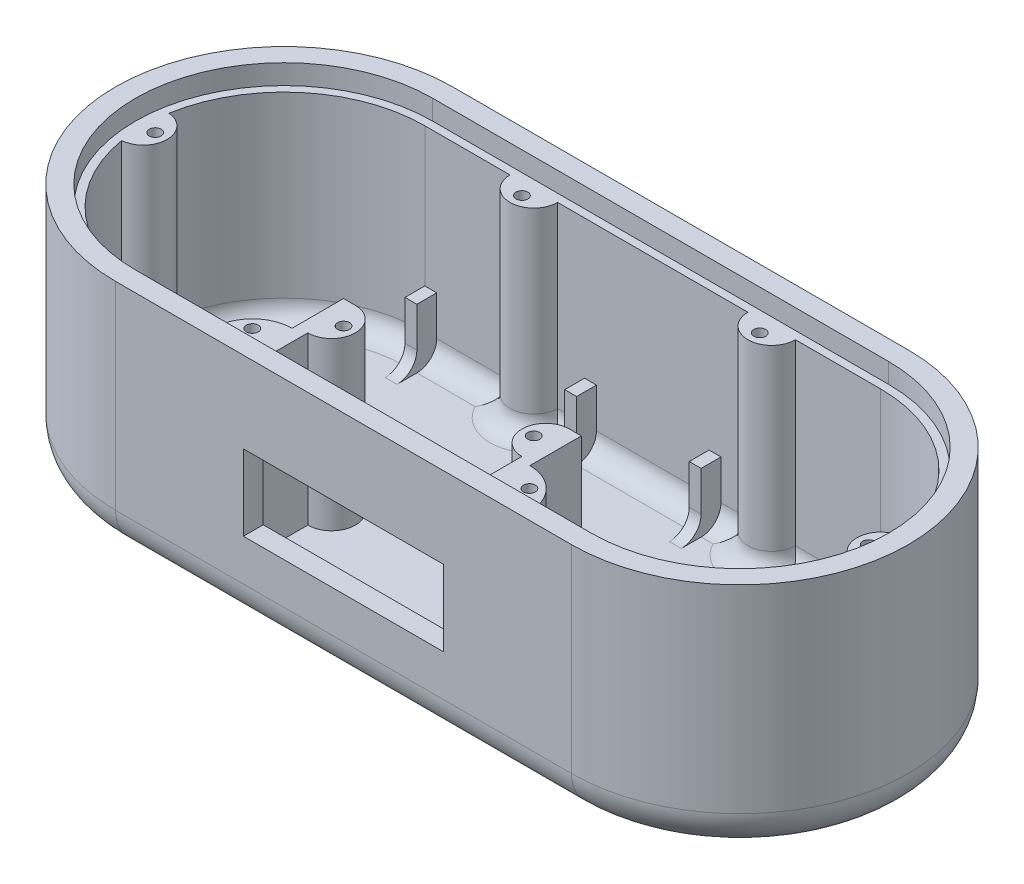
SolidWorks part; units mm, degrees
ref_plane "Front Plane" through (0, 0, 0) normal (0, 0, 1) x (1, 0, 0)
ref_plane "Top Plane" through (0, 0, 0) normal (0, 1, 0) x (1, 0, 0)
ref_plane "Right Plane" through (0, 0, 0) normal (1, 0, 0) x (0, 0, -1)
sketch "Sketch1" plane through (0, 0, 0) normal (0, 1, 0) x (1, 0, 0)
  line L0 (-57.5, 0) -> (57.5, 0) construction
  line L1 (-57.5, 42.5) -> (57.5, 42.5)
  line L2 (-57.5, -42.5) -> (57.5, -42.5)
  line L3 (-57.5, 0) -> (-100, 0) construction
  line L4 (57.5, 0) -> (100, 0) construction
  arc A0 (-57.5, 42.5) -> (-57.5, -42.5) centre (-57.5, 0) ccw
  arc A1 (57.5, -42.5) -> (57.5, 42.5) centre (57.5, 0) ccw
  point P3 (0, 0)
  point P12 (31.5337, 0)
  point P13 (0, 0)
  dimension "D1" = 85
  dimension "D2" = 200
extrude "Boss-Extrude1" add sketch "Sketch1" along normal blind 60
fillet "Fillet1" radius 10 4 edges at (0, 0, 42.5) (100, 0, 0) (0, 0, -42.5) (-100, 0, 0)
sketch "Sketch2" plane through (0, 60, 0) normal (0, 1, 0) x (1, 0, 0)
  line L2 (-57.5, -37.5) -> (-30, -37.5)
  line L3 (-30, -37.5) -> (-30, -12.5)
  line L4 (-57.5, -37.5) -> (57.5, -37.5)
  line L5 (57.5, 37.5) -> (-57.5, 37.5)
  line L7 (57.5, 37.5) -> (-57.5, 37.5)
  line L8 (-30, -12.5) -> (30, -12.5)
  line L9 (30, -12.5) -> (30, -37.5)
  line L10 (30, -37.5) -> (57.5, -37.5)
  line L11 (0, -12.5) -> (0, 0) construction
  arc A4 (-57.5, 37.5) -> (-57.5, -37.5) centre (-57.5, 0) ccw
  arc A5 (57.5, -37.5) -> (57.5, 37.5) centre (57.5, 0) ccw
  arc A6 (-57.5, 37.5) -> (-57.5, -37.5) centre (-57.5, 0) ccw
  arc A7 (57.5, -37.5) -> (57.5, 37.5) centre (57.5, 0) ccw
  dimension "D2" = 25
  dimension "D3" = 60
  dimension "D1" = 5
extrude "Cut-Extrude1" cut sketch "Sketch2" against normal blind 5
sketch "Sketch3" plane through (0, 55, 0) normal (0, 1, 0) x (1, 0, 0)
  line L0 (30, -12.5) -> (30, -37.5) construction
  line L1 (-30, -37.5) -> (-30, -12.5) construction
  line L2 (-30, -25.5) -> (30, -25.5) construction
  line L3 (-40, -35.5) -> (-30, -35.5) construction
  line L4 (40, -35.5) -> (30, -35.5) construction
  line L5 (-37.0711, -28.4289) -> (-30, -35.5) construction
  line L6 (-30, -37.5) -> (-30, -12.5) construction
  line L7 (30, -35.5) -> (37.0711, -28.4289) construction
  line L8 (-30, 32.5) -> (-30, 35.5) construction
  line L9 (30, 35.5) -> (30, 32.5) construction
  line L10 (-36, 35.5) -> (-57.5, 35.5)
  line L11 (24, 35.5) -> (-24, 35.5)
  line L12 (32, -35.5) -> (57.5, -35.5)
  line L13 (57.5, 35.5) -> (-57.5, 35.5)
  line L14 (-57.5, -35.5) -> (-32, -35.5)
  line L15 (-32, -35.5) -> (-32, -10.5)
  line L16 (-32, -10.5) -> (32, -10.5)
  line L17 (32, -10.5) -> (32, -35.5)
  line L18 (40, -35.5) -> (57.5, -35.5)
  line L19 (57.5, 35.5) -> (36, 35.5)
  line L20 (-57.5, -35.5) -> (-40, -35.5)
  line L21 (93, 0) -> (95, 0) construction
  line L24 (-93, 0) -> (-95, 0) construction
  line L25 (-34.9497, -30.5503) -> (34.9497, -30.5503) construction
  line L26 (-90, 0) -> (-87, 0) construction
  line L27 (90, 0) -> (87, 0) construction
  line L28 (30, 32.5) -> (30, 29.5) construction
  line L29 (-30, 32.5) -> (-30, 29.5) construction
  line L30 (-30, 29.5) -> (-30, -12.5) construction
  line L31 (30, 29.5) -> (30, -12.5) construction
  line L32 (-30, -25.5) -> (-30, -12.5)
  line L33 (-30, -12.5) -> (30, -12.5)
  line L34 (30, -12.5) -> (30, -25.5)
  arc A0 (40, -35.5) -> (30, -25.5) centre (30, -35.5) ccw
  arc A1 (-92.493, 5.9785) -> (-92.493, -5.9785) centre (-93, 0) cw
  arc A2 (-30, -25.5) -> (-40, -35.5) centre (-30, -35.5) ccw
  arc A3 (92.493, 5.9785) -> (92.493, -5.9785) centre (93, 0) ccw
  arc A4 (57.5, -35.5) -> (57.5, 35.5) centre (57.5, 0) ccw
  arc A5 (-57.5, 35.5) -> (-57.5, -35.5) centre (-57.5, 0) ccw
  arc A6 (57.5, -35.5) -> (92.493, -5.9785) centre (57.5, 0) ccw
  arc A7 (-57.5, 35.5) -> (-92.493, 5.9785) centre (-57.5, 0) ccw
  arc A8 (24, 35.5) -> (36, 35.5) centre (30, 35.5) ccw
  arc A9 (-36, 35.5) -> (-24, 35.5) centre (-30, 35.5) ccw
  arc A10 (-92.493, -5.9785) -> (-57.5, -35.5) centre (-57.5, 0) ccw
  arc A11 (92.493, 5.9785) -> (57.5, 35.5) centre (57.5, 0) ccw
  arc A12 (57.5, -37.5) -> (57.5, 37.5) centre (57.5, 0) ccw construction
  arc A13 (-57.5, 37.5) -> (-57.5, -37.5) centre (-57.5, 0) ccw construction
  arc A14 (-92.493, 5.9785) -> (-93, 0) centre (-57.5, 0) ccw construction
  arc A15 (-92.493, -5.9785) -> (-93, 0) centre (-57.5, 0) cw construction
  arc A16 (92.493, 5.9785) -> (93, 0) centre (57.5, 0) cw construction
  arc A17 (92.493, -5.9785) -> (93, 0) centre (57.5, 0) ccw construction
  circle A18 centre (-90, 0) radius 1.5
  circle A19 centre (-30, 32.5) radius 1.5
  circle A20 centre (30, 32.5) radius 1.5
  circle A21 centre (90, 0) radius 1.5
  circle A22 centre (34.9497, -30.5503) radius 1.5
  circle A23 centre (-34.9497, -30.5503) radius 1.5
  dimension "D2" = 10
  dimension "D3" = 6
  dimension "D4" = 3
  dimension "D5" = 3
  dimension "D6" = 42
  dimension "D7" = 3
  dimension "D1" = 2
extrude "Cut-Extrude2" cut sketch "Sketch3" against normal offset from surface (50 mm away) 5 up to face at (0, 0, 0)
fillet "Fillet2" radius 5 18 edges at (-48.75, 5, 35.5) (-80.3912, 5, 27.1338) (-87, 5, 0) (-80.3912, 5, -27.1338) (-46.75, 5, -35.5) (-30, 5, -29.5) (0, 5, -35.5) (30, 5, -29.5) (46.75, 5, -35.5) (80.3912, 5, -27.1338) (87, 5, 0) (80.3912, 5, 27.1338) (48.75, 5, 35.5) (37.0711, 5, 28.4289) (30, 5, 19) (0, 5, 12.5) (-30, 5, 19) (-37.0711, 5, 28.4289)
sketch "Sketch4" plane through (0, 55, 0) normal (0, 1, 0) x (1, 0, 0)
  line L5 (-57.5, -30.5) -> (-44.1421, -30.5) construction
  line L10 (-57.5, -35.5) -> (-54.5, -35.5)
  line L11 (-57.5, -35.5) -> (-57.5, -30.5)
  line L12 (-57.5, -30.5) -> (-54.5, -30.5)
  line L13 (-54.5, -35.5) -> (-54.5, -30.5)
  line L14 (24, 35.5) -> (-24, 35.5) construction
  line L15 (-17.202, 35.5) -> (-14.202, 35.5)
  line L16 (-17.202, 35.5) -> (-17.202, 30.5)
  line L17 (-17.202, 30.5) -> (-14.202, 30.5)
  line L18 (-14.202, 35.5) -> (-14.202, 30.5)
  line L19 (20.202, 30.5) -> (-20.202, 30.5) construction
  line L20 (-39.798, 30.5) -> (-57.5, 30.5) construction
  line L21 (17.202, 35.5) -> (14.202, 35.5)
  line L22 (17.202, 35.5) -> (17.202, 30.5)
  line L23 (17.202, 30.5) -> (14.202, 30.5)
  line L24 (14.202, 35.5) -> (14.202, 30.5)
  line L25 (-57.5, 35.5) -> (-54.5, 35.5)
  line L26 (-57.5, 35.5) -> (-57.5, 30.5)
  line L27 (-57.5, 30.5) -> (-54.5, 30.5)
  line L28 (-54.5, 35.5) -> (-54.5, 30.5)
  line L29 (57.5, 30.5) -> (39.798, 30.5) construction
  line L30 (57.5, 35.5) -> (54.5, 35.5)
  line L31 (57.5, 35.5) -> (57.5, 30.5)
  line L32 (57.5, 30.5) -> (54.5, 30.5)
  line L33 (54.5, 35.5) -> (54.5, 30.5)
  line L34 (44.1421, -30.5) -> (57.5, -30.5) construction
  line L35 (57.5, -35.5) -> (54.5, -35.5)
  line L36 (57.5, -35.5) -> (57.5, -30.5)
  line L37 (57.5, -30.5) -> (54.5, -30.5)
  line L38 (54.5, -35.5) -> (54.5, -30.5)
  dimension "D1" = 3
  dimension "D2" = 3
  dimension "D3" = 3
extrude "Boss-Extrude2" add sketch "Sketch4" against normal up to surface (50 mm away) up to face at (0, 5, 0.3691)
sketch "Sketch5" plane through (0, 55, 0) normal (0, 1, 0) x (1, 0, 0)
  line L1 (-57.5, 30.5) -> (-54.5, 30.5)
  line L2 (-57.5, 30.5) -> (-57.5, 35.5)
  line L3 (-57.5, 35.5) -> (-54.5, 35.5)
  line L4 (-54.5, 30.5) -> (-54.5, 35.5)
  line L5 (-17.202, 30.5) -> (-14.202, 30.5)
  line L6 (-17.202, 30.5) -> (-17.202, 35.5)
  line L7 (-17.202, 35.5) -> (-14.202, 35.5)
  line L8 (-14.202, 30.5) -> (-14.202, 35.5)
  line L9 (14.202, 30.5) -> (17.202, 30.5)
  line L10 (14.202, 30.5) -> (14.202, 35.5)
  line L11 (14.202, 35.5) -> (17.202, 35.5)
  line L12 (17.202, 30.5) -> (17.202, 35.5)
  line L13 (54.5, 30.5) -> (57.5, 30.5)
  line L14 (54.5, 30.5) -> (54.5, 35.5)
  line L15 (54.5, 35.5) -> (57.5, 35.5)
  line L16 (57.5, 30.5) -> (57.5, 35.5)
  line L17 (54.5, -30.5) -> (57.5, -30.5)
  line L18 (54.5, -30.5) -> (54.5, -35.5)
  line L19 (54.5, -35.5) -> (57.5, -35.5)
  line L20 (57.5, -30.5) -> (57.5, -35.5)
  line L21 (-57.5, -30.5) -> (-54.5, -30.5)
  line L22 (-57.5, -30.5) -> (-57.5, -35.5)
  line L23 (-57.5, -35.5) -> (-54.5, -35.5)
  line L24 (-54.5, -30.5) -> (-54.5, -35.5)
extrude "Cut-Extrude3" cut sketch "Sketch5" against normal offset from surface (35 mm away) 15 up to face at (0, 5, -4.4367)
fillet "Fillet3" radius 5 6 edges at (15.702, 5, -30.5) (-56, 5, 30.5) (56, 5, 30.5) (56, 5, -30.5) (-15.702, 5, -30.5) (-56, 5, -30.5)
sketch "Sketch6" plane through (0, 5, 0) normal (0, 1, 0) x (1, 0, 0)
  circle A0 centre (-57.5, 0) radius 3
  circle A1 centre (-57.5, 0) radius 1.5
  circle A2 centre (57.5, 0) radius 3
  circle A3 centre (57.5, 0) radius 1.5
  arc A4 (-57.5, 30.5) -> (-86.6479, 8.9806) centre (-57.5, 0) ccw construction
  arc A5 (86.6479, 8.9806) -> (57.5, 30.5) centre (57.5, 0) ccw construction
  dimension "D1" = 3
  dimension "D2" = 6
extrude "Boss-Extrude3" add sketch "Sketch6" along normal up to surface (15 mm away) up to face at (-56, 20, -33)
fillet "Fillet4" radius 1 2 edges at (57.5, 5, 3) (-57.5, 5, 3)
sketch "Sketch8" plane through (0, 0, 12.5) normal (0, 0, -1) x (-1, 0, 0)
  line L5 (-57.5, 60) -> (57.5, 60) construction
  line L6 (-30, 60) -> (30, 60)
  line L8 (-27, 57) -> (-27, 13)
  line L9 (-27, 13) -> (27, 13)
  line L10 (27, 13) -> (27, 57)
  line L11 (27, 57) -> (-27, 57)
  line L12 (-27, 57) -> (-27, 13)
  line L13 (-27, 13) -> (27, 13)
  line L14 (27, 13) -> (27, 57)
  line L16 (30, 60) -> (-30, 60) construction
  line L17 (27, 57) -> (30, 57)
  line L18 (30, 10) -> (30, 60) construction
  line L19 (30, 57) -> (30, 60)
  line L20 (-27, 57) -> (-30, 57)
  line L21 (-30, 10) -> (-30, 60) construction
  line L22 (-30, 57) -> (-30, 60)
  dimension "D1" = 3
extrude "Cut-Extrude4" cut sketch "Sketch8" against normal offset from surface (25 mm away) 5 up to face at (0, 35, 42.5)
sketch "Sketch10" plane through (0, 0, 37.5) normal (0, 0, -1) x (-1, 0, 0)
  line L5 (0, 39.55) -> (0, 60) construction
  line L7 (-25.25, 39.55) -> (25.25, 39.55)
  line L9 (-25.25, 39.55) -> (-25.25, 20.45)
  line L10 (-25.25, 20.45) -> (25.25, 20.45)
  line L11 (25.25, 39.55) -> (25.25, 20.45)
  line L12 (-57.5, 60) -> (57.5, 60) construction
  line L13 (0, 20.45) -> (0, 0) construction
  dimension "D1" = 19.1
  dimension "D2" = 50.5
extrude "Cut-Extrude5" cut sketch "Sketch10" against normal blind 5
sketch "Sketch12" plane through (0, 13, 0) normal (0, 1, 0) x (1, 0, 0)
  line L0 (27, -37.5) -> (27, -12.5) construction
  line L1 (-27, -37.5) -> (-27, -12.5) construction
  line L2 (30, -12.5) -> (-30, -12.5) construction
  line L3 (-27, -37.5) -> (-27, -12.5) construction
  line L4 (-21, -18.5) -> (-24, -18.5) construction
  line L5 (21, -18.5) -> (24, -18.5) construction
  line L7 (-27, -24.5) -> (-27, -12.5)
  line L8 (27, -24.5) -> (27, -12.5)
  arc A0 (27, -12.5) -> (27, -24.5) centre (27, -18.5) ccw
  arc A1 (-27, -12.5) -> (-27, -24.5) centre (-27, -18.5) cw
  circle A2 centre (-24, -18.5) radius 1.5
  circle A3 centre (24, -18.5) radius 1.5
  dimension "D1" = 6
  dimension "D3" = 3
  dimension "D2" = 3
extrude "Boss-Extrude5" add sketch "Sketch12" along normal up to surface (44 mm away) up to face at (28.5, 57, 25)
sketch "Sketch13" plane through (0, 57, 0) normal (0, 1, 0) x (1, 0, 0)
  line L12 (-30, -37.5) -> (-27, -37.5)
  line L13 (-27, -37.5) -> (-27, -24.5)
  line L14 (-27, -12.5) -> (-30, -12.5)
  line L15 (-30, -12.5) -> (-30, -37.5)
  line L16 (-30, -37.5) -> (-27, -37.5)
  line L17 (-27, -37.5) -> (-27, -24.5)
  line L18 (-27, -12.5) -> (-30, -12.5)
  line L19 (-30, -12.5) -> (-30, -37.5)
  line L24 (27, -37.5) -> (30, -37.5)
  line L25 (30, -37.5) -> (30, -12.5)
  line L26 (30, -12.5) -> (27, -12.5)
  line L27 (27, -24.5) -> (27, -37.5)
  line L28 (27, -37.5) -> (30, -37.5)
  line L29 (30, -37.5) -> (30, -12.5)
  line L30 (30, -12.5) -> (27, -12.5)
  line L31 (27, -24.5) -> (27, -37.5)
  arc A3 (-27, -24.5) -> (-27, -12.5) centre (-27, -18.5) ccw
  arc A4 (-27, -24.5) -> (-27, -12.5) centre (-27, -18.5) ccw
  arc A6 (27, -12.5) -> (27, -24.5) centre (27, -18.5) ccw
  arc A7 (27, -12.5) -> (27, -24.5) centre (27, -18.5) ccw
  dimension "D1" = 0
  dimension "D2" = 0
extrude "Cut-Extrude6" cut sketch "Sketch13" against normal up to surface (2 mm away) up to face at (0, 55, 2.8572)
